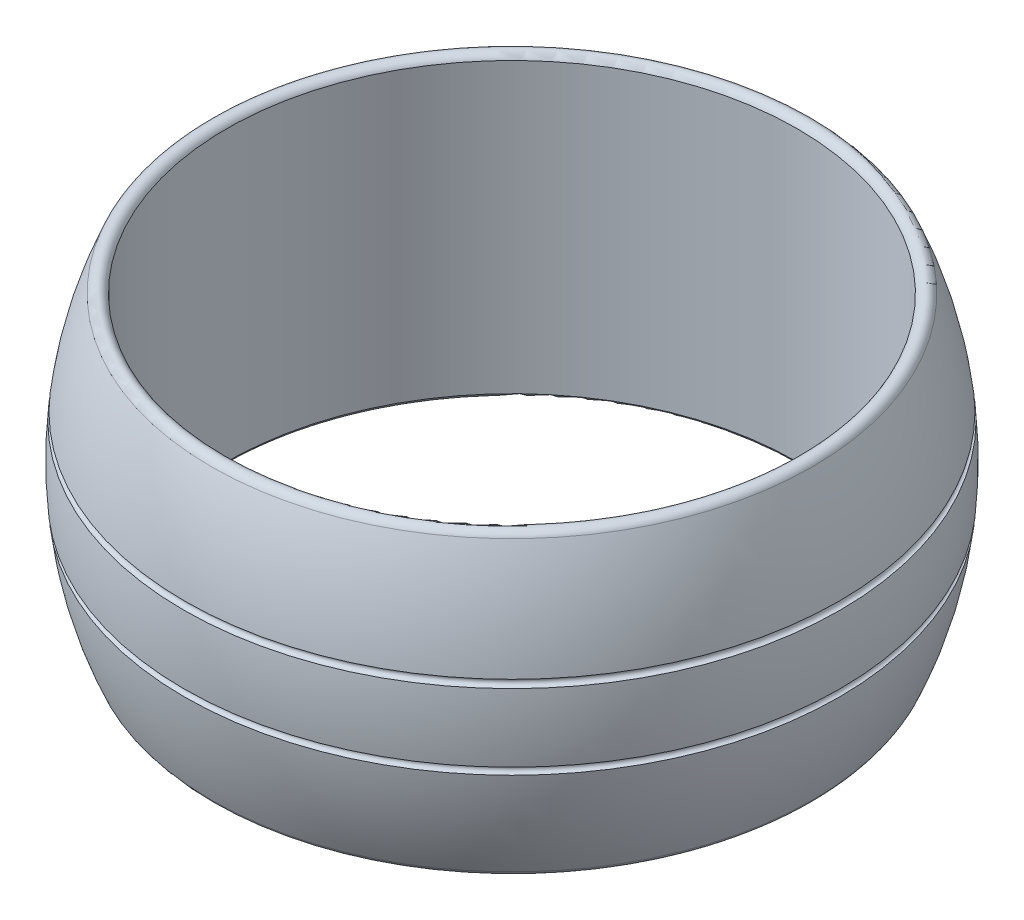
SolidWorks part; units mm, degrees
material "Brass"
ref_plane "Front" through (0, 0, 0) normal (0, 0, 1) x (1, 0, 0)
ref_plane "Top" through (0, 0, 0) normal (0, 1, 0) x (1, 0, 0)
ref_plane "Right" through (0, 0, 0) normal (1, 0, 0) x (0, 0, -1)
ref_axis "Axis1" through (0, 55, 0) along (0, -1, 0)
ref_axis "Axis2" through (88.99, 0, 0) along (-1, 0, 0)
ref_axis "Axis3" through (0, 0, 55) along (0, 0, -1)
sketch "Sketch1" plane through (0, 0, 0) normal (0, 0, 1) x (1, 0, 0)
  line L0 (0, 3.8175) -> (0, -3.8175) construction
  line L1 (7.55, 3.8175) -> (7.55, -3.8175)
  line L2 (7.95, 3.8175) -> (7.95, -3.8175) construction
  line L3 (8.6738, 1) -> (8.6738, -1) construction
  arc A0 (7.95, 3.8175) -> (8.6631, 1.0994) centre (-1.0646, 0) cw
  arc A1 (7.55, -3.8175) -> (7.95, -3.8175) centre (7.75, -3.7328) ccw
  arc A2 (7.95, 3.8175) -> (7.55, 3.8175) centre (7.75, 3.7328) ccw
  arc A3 (8.6631, 1.0994) -> (8.6835, 0.9005) centre (8.6738, 1) ccw
  arc A4 (8.6835, -0.9005) -> (8.6631, -1.0994) centre (8.6738, -1) ccw
  arc A5 (8.6835, 0.9005) -> (8.6835, -0.9005) centre (-1.0646, 0) cw
  arc A6 (8.6631, -1.0994) -> (7.95, -3.8175) centre (-1.0646, 0) cw
  point P9 (7.95, 0)
  point P13 (8.6738, 0)
  dimension "D3" = 17.45
  dimension "D4" = 0.4
  dimension "D1" = 7.9
  dimension "D6" = 0.2
  dimension "D2" = 15.1
  dimension "D5" = 2
revolve "Revolve1" add sketch "Sketch1" angle 360 about L0
